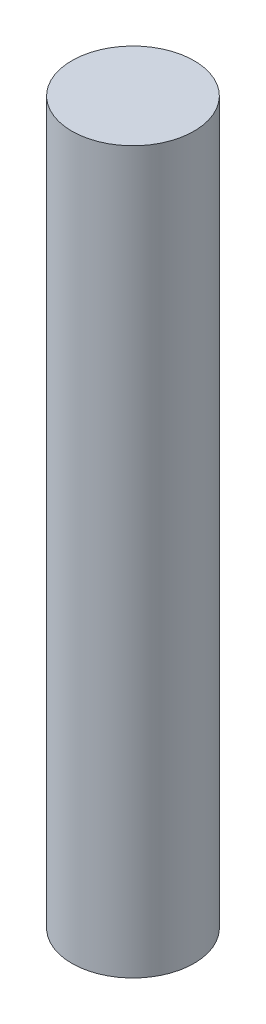
SolidWorks part; units mm, degrees
ref_plane "Front Plane" through (0, 0, 0) normal (0, 0, 1) x (1, 0, 0)
ref_plane "Top Plane" through (0, 0, 0) normal (0, 1, 0) x (1, 0, 0)
ref_plane "Right Plane" through (0, 0, 0) normal (1, 0, 0) x (0, 0, -1)
sketch "Sketch1" plane through (0, 0, 0) normal (0, 1, 0) x (1, 0, 0)
  circle A0 centre (0, 0) radius 2.25
  dimension "D1" = 4.5
sketch "Sketch2" plane through (0, 0, 0) normal (1, 0, 0) x (0, 0, -1)
  line L0 (0, 0) -> (0, 26.5405)
  circle A0 centre (0, 0) radius 26.5405 construction
  point P3 (0, 0)
extrude "Boss-Extrude1" add sketch "Sketch1" along normal up to vertex (26.5405 mm away) contours A0 up to point (0, 26.5405, 0)
